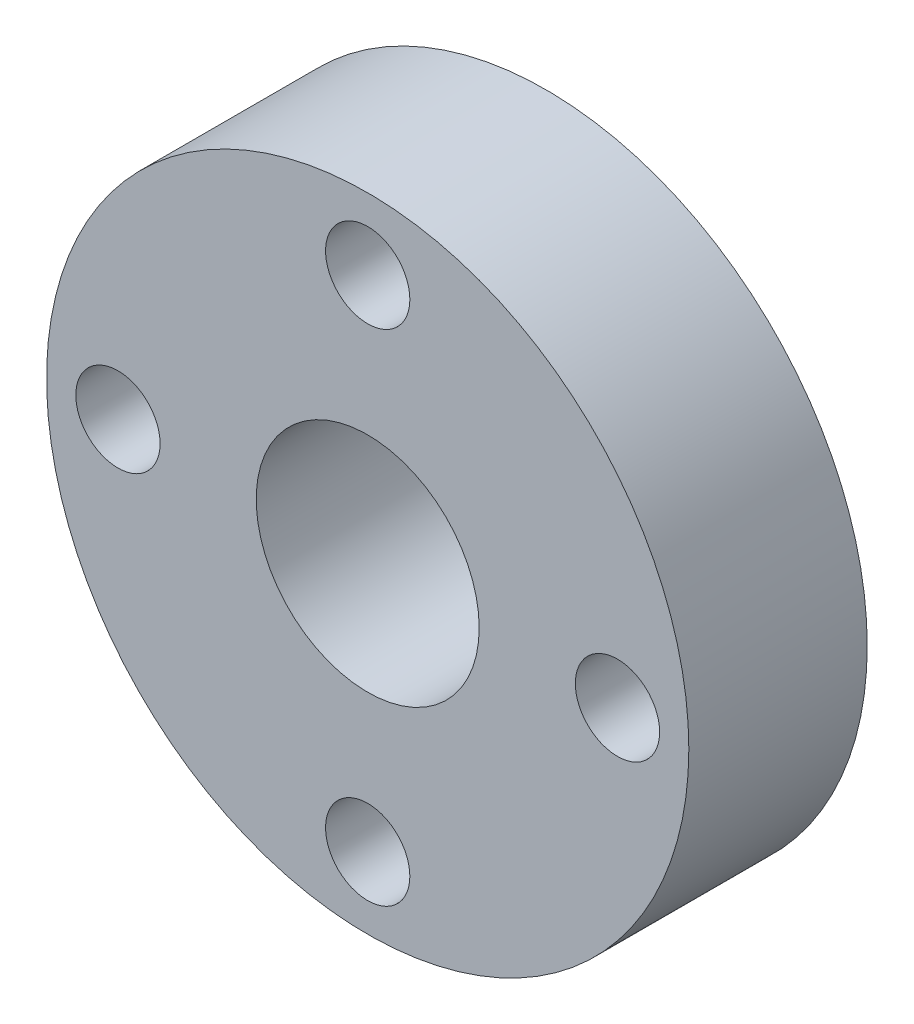
SolidWorks part; units mm, degrees
ref_plane "Front Plane" through (0, 0, 0) normal (0, 0, 1) x (1, 0, 0)
ref_plane "Top Plane" through (0, 0, 0) normal (0, 1, 0) x (1, 0, 0)
ref_plane "Right Plane" through (0, 0, 0) normal (1, 0, 0) x (0, 0, -1)
sketch "Sketch1" plane through (0, 0, 0) normal (0, 0, 1) x (1, 0, 0)
  circle A0 centre (0, 0) radius 11.43
  circle A1 centre (0, 0) radius 3.9688
extrude "Boss-Extrude1" add sketch "Sketch1" along normal blind 6.35
sketch "Sketch4" plane through (0, 0, 6.35) normal (0, 0, 1) x (1, 0, 0)
  line L0 (0, -55) -> (0, 55) construction
  point P0 (0, 8.89)
  point P4 (0, 0)
hole_wizard "Ø3.0mm Dowel Hole1" positions "Sketch4" profile "Sketch5" hole size "Ø3.0" standard "ANSI Metric" end condition through all
sketch "Sketch5" plane through (0, 8.89, 6.35) normal (1, 0, 0) x (0, -1, 0)
  line L0 (0, 0) -> (0, 6.35)
  line L1 (0, 6.35) -> (1.5, 6.35)
  line L2 (1.5, 6.35) -> (1.5, 0)
  line L5 (1.5, 0) -> (0, 0)
  line L11 (0, -6.35) -> (0, 107.95) construction
  dimension "Thru Hole Dia." = 3
  dimension "Thru Hole Depth" = 6.35
pattern_circular "CirPattern1" count 4 over 360 about axis through (0, 0, 6.35) along (0, 0, -1) of "Ø3.0mm Dowel Hole1" reverse direction yes
